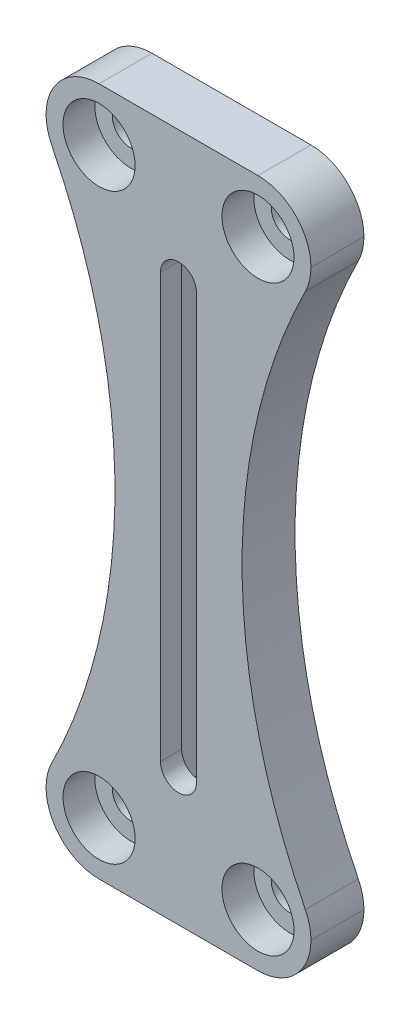
SolidWorks part; units mm, degrees
ref_plane "Plano frontal" through (0, 0, 0) normal (0, 0, 1) x (1, 0, 0)
ref_plane "Plano superior" through (0, 0, 0) normal (0, 1, 0) x (1, 0, 0)
ref_plane "Plano direito" through (0, 0, 0) normal (1, 0, 0) x (0, 0, -1)
sketch "Esboço1" plane through (0, 0, 0) normal (0, 0, 1) x (1, 0, 0)
  line L0 (0, 22.5354) -> (0, 0) construction
  line L1 (-12.5, -32.5) -> (12.5, -32.5)
  line L2 (-12.5, -32.5) -> (-12.5, 32.5)
  line L3 (-12.5, 32.5) -> (12.5, 32.5)
  line L4 (12.5, -32.5) -> (12.5, 32.5)
  line L5 (-12.5, -32.5) -> (12.5, 32.5) construction
  line L6 (-12.5, 32.5) -> (12.5, -32.5) construction
  line L7 (0, 0) -> (9.6084, 0) construction
  line L8 (0, -20) -> (0, 20) construction
  line L9 (-1.7, -20) -> (-1.7, 20)
  line L10 (1.7, -20) -> (1.7, 20)
  circle A0 centre (7.5, 27.5) radius 1.75
  circle A1 centre (7.5, -27.5) radius 1.75
  circle A2 centre (-7.5, -27.5) radius 1.75
  circle A3 centre (-7.5, 27.5) radius 1.75
  arc A4 (-1.7, -20) -> (1.7, -20) centre (0, -20) ccw
  arc A5 (1.7, 20) -> (-1.7, 20) centre (0, 20) ccw
  point P0 (0, 0)
  point P20 (0, 0)
  dimension "D5" = 3.5
  dimension "D6" = 1.7
  dimension "D1" = 55
  dimension "D2" = 15
  dimension "D3" = 5
  dimension "D4" = 5
  dimension "D7" = 40
extrude "Ressalto-extrusão1" add sketch "Esboço1" along normal blind 5
sketch "Esboço4" plane through (0, 0, 5) normal (0, 0, 1) x (1, 0, 0)
  line L0 (12.5, 27.5) -> (12.5, -27.5)
  line L1 (12.5, -32.5) -> (12.5, 32.5) construction
  line L2 (0, 0) -> (15.0343, 0) construction
  line L3 (0, 0) -> (0, 13.8608) construction
  line L4 (-12.5, 27.5) -> (-12.5, -27.5)
  arc A0 (11.9709, 25.2614) -> (11.9709, -25.2614) centre (62.4231, 0) ccw
  arc A1 (12.5, -27.5) -> (11.9709, -25.2614) centre (7.5, -27.5) ccw
  arc A2 (12.5, 27.5) -> (11.9709, 25.2614) centre (7.5, 27.5) cw
  arc A3 (-12.5, 27.5) -> (-11.9709, 25.2614) centre (-7.5, 27.5) ccw
  arc A4 (-12.5, -27.5) -> (-11.9709, -25.2614) centre (-7.5, -27.5) cw
  arc A5 (-11.9709, 25.2614) -> (-11.9709, -25.2614) centre (-62.4231, 0) cw
  point P7 (12.5, 0)
  point P14 (12.5, 0)
  point P15 (15.0343, 0)
  point P25 (-12.5, 0)
  dimension "D1" = 6
extrude "Corte-extrusão3" cut sketch "Esboço4" against normal through all both and the other way through all
fillet "Filete1" radius 5 4 edges at (-12.5, -32.5, 2.5) (12.5, -32.5, 2.5) (12.5, 32.5, 2.5) (-12.5, 32.5, 2.5)
sketch "Esboço2" plane through (0, 0, 5) normal (0, 0, 1) x (1, 0, 0)
  circle A0 centre (7.5, 27.5) radius 3.4
  circle A1 centre (-7.5, 27.5) radius 3.4
  circle A2 centre (-7.5, -27.5) radius 3.4
  circle A3 centre (7.5, -27.5) radius 3.4
  dimension "D1" = 6.8
extrude "Corte-extrusão1" cut sketch "Esboço2" against normal blind 3
sketch "Esboço3" plane through (0, 0, 0) normal (0, 0, -1) x (-1, 0, 0)
  line L1 (-2.8, -24) -> (2.8, -24)
  line L2 (-2.8, -24) -> (-2.8, 24)
  line L3 (-2.8, 24) -> (2.8, 24)
  line L4 (2.8, -24) -> (2.8, 24)
  line L5 (-2.8, -24) -> (2.8, 24) construction
  line L6 (-2.8, 24) -> (2.8, -24) construction
  arc A0 (1.7, 20) -> (-1.7, 20) centre (0, 20) ccw construction
  point P0 (0, 0)
  dimension "D1" = 5.6
  dimension "D2" = 4
extrude "Corte-extrusão2" cut sketch "Esboço3" against normal blind 3
equation "\"D4@Esboço1\"=\"D3@Esboço1\""
